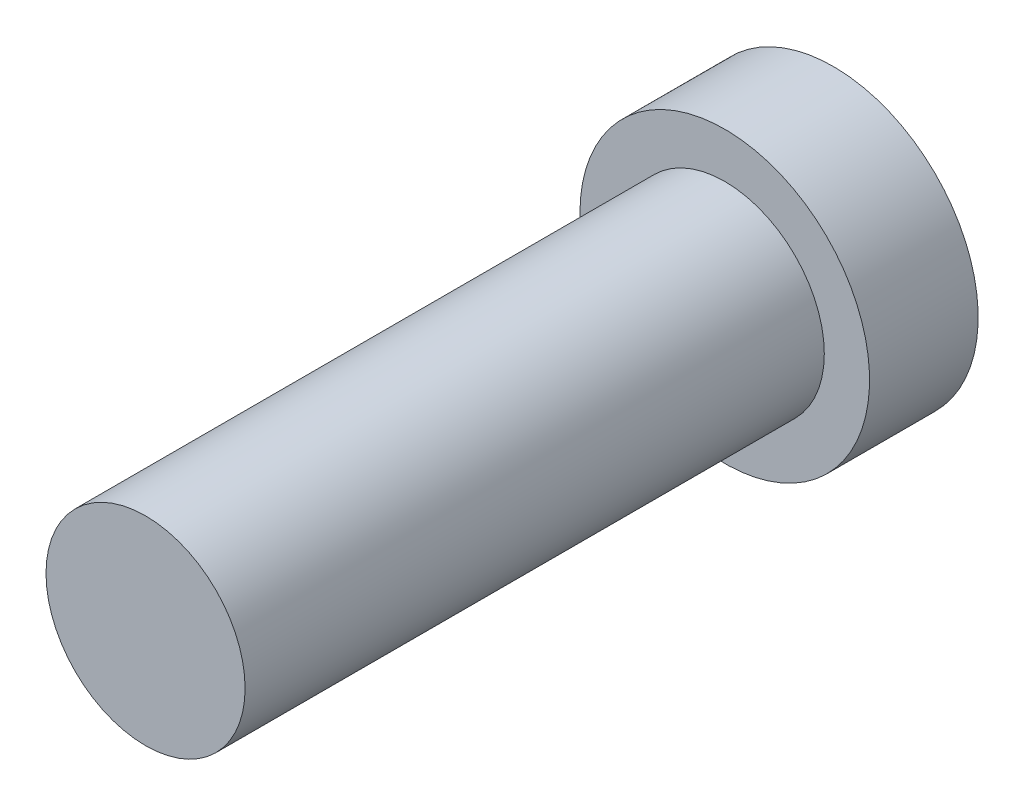
SolidWorks part; units mm, degrees
material "ABS"
ref_plane "Front Plane" through (0, 0, 0) normal (0, 0, 1) x (1, 0, 0)
ref_plane "Top Plane" through (0, 0, 0) normal (0, 1, 0) x (1, 0, 0)
ref_plane "Right Plane" through (0, 0, 0) normal (1, 0, 0) x (0, 0, -1)
sketch "Sketch2" plane through (0, 0, 0) normal (0, 0, 1) x (1, 0, 0)
  circle A0 centre (0, 0) radius 1.375
extrude "Boss-Extrude1" add sketch "Sketch2" along normal blind 8
ref_axis "Axis1" through (0, 0, 0) along (0, 0, -1)
sketch "Sketch3" plane through (0, 0, 0) normal (0, 0, -1) x (-1, 0, 0)
  circle A2 centre (0, 0) radius 2
  point P8 (0, 0)
extrude "Boss-Extrude2" add sketch "Sketch3" along normal blind 1.5 contours A2
